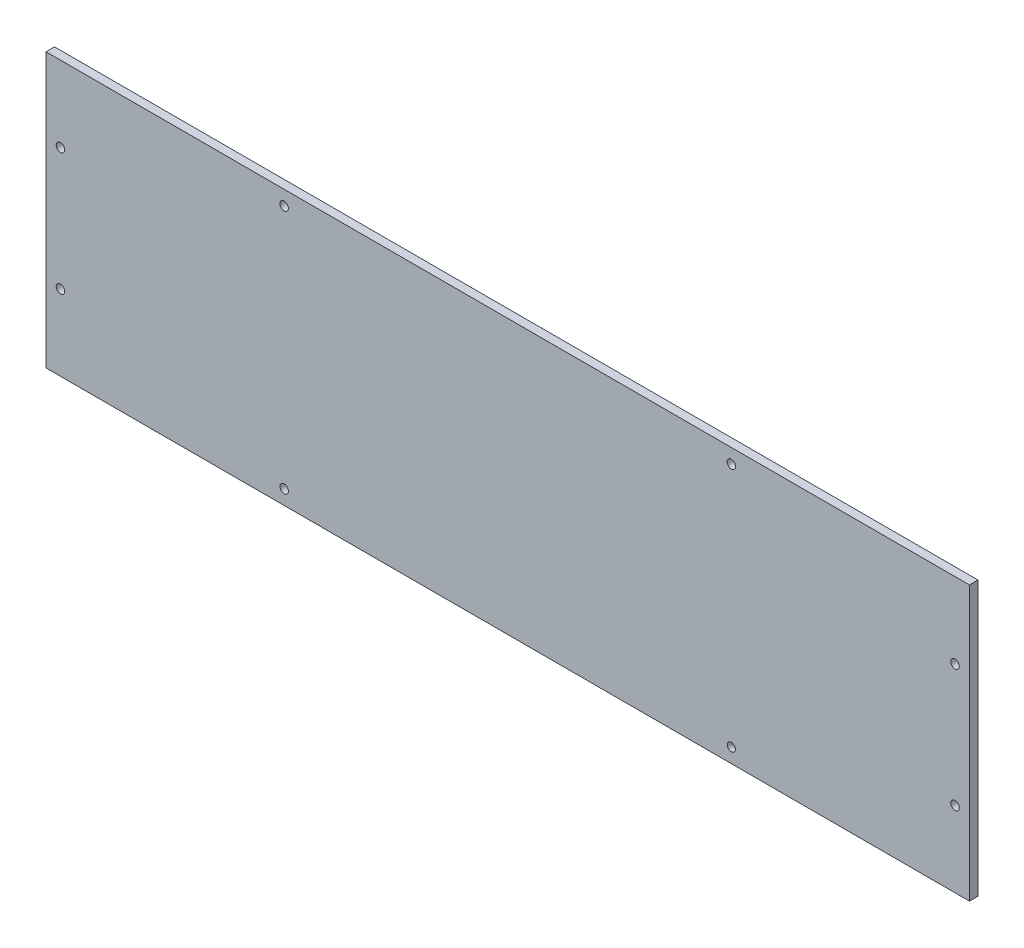
SolidWorks part; units mm, degrees
material "Acrylic (Medium-high impact)"
ref_plane "Front Plane" through (0, 0, 0) normal (0, 0, 1) x (1, 0, 0)
ref_plane "Top Plane" through (0, 0, 0) normal (0, 1, 0) x (1, 0, 0)
ref_plane "Right Plane" through (0, 0, 0) normal (1, 0, 0) x (0, 0, -1)
sketch "Model" plane through (0, 0, 0) normal (0, 0, 1) x (1, 0, 0)
  line L0 (0.0937, 96.2808) -> (324.895, 96.2808)
  line L1 (324.895, 96.2808) -> (324.895, 0.0799)
  line L2 (324.895, 0.0799) -> (0.0937, 0.0799)
  line L3 (0.0937, 0.0799) -> (0.0937, 96.2808)
  line L4 (129.892, 26.056) -> (133.194, 26.056)
  line L5 (133.194, 26.056) -> (133.194, 11.8553)
  line L6 (133.194, 11.8553) -> (129.892, 11.8553)
  line L7 (129.892, 11.8553) -> (129.892, 26.056)
  line L8 (153.694, 26.056) -> (156.994, 26.056)
  line L9 (156.994, 26.056) -> (156.994, 11.8553)
  line L10 (156.994, 11.8553) -> (153.694, 11.8553)
  line L11 (153.694, 11.8553) -> (153.694, 26.056)
  line L12 (167.992, 26.056) -> (171.294, 26.056)
  line L13 (171.294, 26.056) -> (171.294, 11.8553)
  line L14 (171.294, 11.8553) -> (167.992, 11.8553)
  line L15 (167.992, 11.8553) -> (167.992, 26.056)
  line L16 (191.794, 26.056) -> (195.094, 26.056)
  line L17 (195.094, 26.056) -> (195.094, 11.8553)
  line L18 (195.094, 11.8553) -> (191.794, 11.8553)
  line L19 (191.794, 11.8553) -> (191.794, 26.056)
  line L20 (12.6187, 26.6058) -> (26.6182, 26.6058)
  line L21 (26.6182, 26.6058) -> (26.6182, 12.6063)
  line L22 (26.6182, 12.6063) -> (12.6187, 12.6063)
  line L23 (12.6187, 12.6063) -> (12.6187, 26.6058)
  line L24 (31.6687, 26.6058) -> (45.6681, 26.6058)
  line L25 (45.6681, 26.6058) -> (45.6681, 12.6063)
  line L26 (45.6681, 12.6063) -> (31.6687, 12.6063)
  line L27 (31.6687, 12.6063) -> (31.6687, 26.6058)
  line L28 (50.7189, 26.6058) -> (64.7181, 26.6058)
  line L29 (64.7181, 26.6058) -> (64.7181, 12.6063)
  line L30 (64.7181, 12.6063) -> (50.7189, 12.6063)
  line L31 (50.7189, 12.6063) -> (50.7189, 26.6058)
  line L32 (69.7689, 26.6058) -> (83.7681, 26.6058)
  line L33 (83.7681, 26.6058) -> (83.7681, 12.6063)
  line L34 (83.7681, 12.6063) -> (69.7689, 12.6063)
  line L35 (69.7689, 12.6063) -> (69.7689, 26.6058)
  line L36 (136.444, 26.6058) -> (150.443, 26.6058)
  line L37 (150.443, 26.6058) -> (150.443, 12.6063)
  line L38 (150.443, 12.6063) -> (136.444, 12.6063)
  line L39 (136.444, 12.6063) -> (136.444, 26.6058)
  line L40 (174.544, 26.6058) -> (188.543, 26.6058)
  line L41 (188.543, 26.6058) -> (188.543, 12.6063)
  line L42 (188.543, 12.6063) -> (174.544, 12.6063)
  line L43 (174.544, 12.6063) -> (174.544, 26.6058)
  line L44 (241.219, 26.6058) -> (255.218, 26.6058)
  line L45 (255.218, 26.6058) -> (255.218, 12.6063)
  line L46 (255.218, 12.6063) -> (241.219, 12.6063)
  line L47 (241.219, 12.6063) -> (241.219, 26.6058)
  line L48 (260.269, 26.6058) -> (274.268, 26.6058)
  line L49 (274.268, 26.6058) -> (274.268, 12.6063)
  line L50 (274.268, 12.6063) -> (260.269, 12.6063)
  line L51 (260.269, 12.6063) -> (260.269, 26.6058)
  line L52 (279.319, 26.6058) -> (293.318, 26.6058)
  line L53 (293.318, 26.6058) -> (293.318, 12.6063)
  line L54 (293.318, 12.6063) -> (279.319, 12.6063)
  line L55 (279.319, 12.6063) -> (279.319, 26.6058)
  line L56 (298.369, 26.6058) -> (312.368, 26.6058)
  line L57 (312.368, 26.6058) -> (312.368, 12.6063)
  line L58 (312.368, 12.6063) -> (298.369, 12.6063)
  line L59 (298.369, 12.6063) -> (298.369, 26.6058)
  line L60 (15.5925, 45.1058) -> (18.8929, 45.1058)
  line L61 (18.8929, 45.1058) -> (18.8929, 30.9053)
  line L62 (18.8929, 30.9053) -> (15.5925, 30.9053)
  line L63 (15.5925, 30.9053) -> (15.5925, 45.1058)
  line L64 (39.394, 45.1058) -> (42.6932, 45.1058)
  line L65 (42.6932, 45.1058) -> (42.6932, 30.9053)
  line L66 (42.6932, 30.9053) -> (39.394, 30.9053)
  line L67 (39.394, 30.9053) -> (39.394, 45.1058)
  line L68 (282.294, 45.1058) -> (285.594, 45.1058)
  line L69 (285.594, 45.1058) -> (285.594, 30.9053)
  line L70 (285.594, 30.9053) -> (282.294, 30.9053)
  line L71 (282.294, 30.9053) -> (282.294, 45.1058)
  line L72 (306.094, 45.1058) -> (309.394, 45.1058)
  line L73 (309.394, 45.1058) -> (309.394, 30.9053)
  line L74 (309.394, 30.9053) -> (306.094, 30.9053)
  line L75 (306.094, 30.9053) -> (306.094, 45.1058)
  line L76 (22.1423, 45.6558) -> (36.1431, 45.6558)
  line L77 (36.1431, 45.6558) -> (36.1431, 31.6563)
  line L78 (36.1431, 31.6563) -> (22.1423, 31.6563)
  line L79 (22.1423, 31.6563) -> (22.1423, 45.6558)
  line L80 (50.7189, 45.6558) -> (64.7181, 45.6558)
  line L81 (64.7181, 45.6558) -> (64.7181, 31.6563)
  line L82 (64.7181, 31.6563) -> (50.7189, 31.6563)
  line L83 (50.7189, 31.6563) -> (50.7189, 45.6558)
  line L84 (69.7689, 45.6558) -> (83.7681, 45.6558)
  line L85 (83.7681, 45.6558) -> (83.7681, 31.6563)
  line L86 (83.7681, 31.6563) -> (69.7689, 31.6563)
  line L87 (69.7689, 31.6563) -> (69.7689, 45.6558)
  line L88 (88.8189, 45.6558) -> (102.818, 45.6558)
  line L89 (102.818, 45.6558) -> (102.818, 31.6563)
  line L90 (102.818, 31.6563) -> (88.8189, 31.6563)
  line L91 (88.8189, 31.6563) -> (88.8189, 45.6558)
  line L92 (107.867, 45.6558) -> (121.868, 45.6558)
  line L93 (121.868, 45.6558) -> (121.868, 31.6563)
  line L94 (121.868, 31.6563) -> (107.867, 31.6563)
  line L95 (107.867, 31.6563) -> (107.867, 45.6558)
  line L96 (126.919, 45.6558) -> (140.918, 45.6558)
  line L97 (140.918, 45.6558) -> (140.918, 31.6563)
  line L98 (140.918, 31.6563) -> (126.919, 31.6563)
  line L99 (126.919, 31.6563) -> (126.919, 45.6558)
  line L100 (145.969, 45.6558) -> (159.968, 45.6558)
  line L101 (159.968, 45.6558) -> (159.968, 31.6563)
  line L102 (159.968, 31.6563) -> (145.969, 31.6563)
  line L103 (145.969, 31.6563) -> (145.969, 45.6558)
  line L104 (165.019, 45.6558) -> (179.018, 45.6558)
  line L105 (179.018, 45.6558) -> (179.018, 31.6563)
  line L106 (179.018, 31.6563) -> (165.019, 31.6563)
  line L107 (165.019, 31.6563) -> (165.019, 45.6558)
  line L108 (184.069, 45.6558) -> (198.068, 45.6558)
  line L109 (198.068, 45.6558) -> (198.068, 31.6563)
  line L110 (198.068, 31.6563) -> (184.069, 31.6563)
  line L111 (184.069, 31.6563) -> (184.069, 45.6558)
  line L112 (203.119, 45.6558) -> (217.118, 45.6558)
  line L113 (217.118, 45.6558) -> (217.118, 31.6563)
  line L114 (217.118, 31.6563) -> (203.119, 31.6563)
  line L115 (203.119, 31.6563) -> (203.119, 45.6558)
  line L116 (222.169, 45.6558) -> (236.168, 45.6558)
  line L117 (236.168, 45.6558) -> (236.168, 31.6563)
  line L118 (236.168, 31.6563) -> (222.169, 31.6563)
  line L119 (222.169, 31.6563) -> (222.169, 45.6558)
  line L120 (241.219, 45.6558) -> (255.218, 45.6558)
  line L121 (255.218, 45.6558) -> (255.218, 31.6563)
  line L122 (255.218, 31.6563) -> (241.219, 31.6563)
  line L123 (241.219, 31.6563) -> (241.219, 45.6558)
  line L124 (260.269, 45.6558) -> (274.268, 45.6558)
  line L125 (274.268, 45.6558) -> (274.268, 31.6563)
  line L126 (274.268, 31.6563) -> (260.269, 31.6563)
  line L127 (260.269, 31.6563) -> (260.269, 45.6558)
  line L128 (288.844, 45.6558) -> (302.843, 45.6558)
  line L129 (302.843, 45.6558) -> (302.843, 31.6563)
  line L130 (302.843, 31.6563) -> (288.844, 31.6563)
  line L131 (288.844, 31.6563) -> (288.844, 45.6558)
  line L132 (12.6187, 64.7058) -> (26.6182, 64.7058)
  line L133 (26.6182, 64.7058) -> (26.6182, 50.7062)
  line L134 (26.6182, 50.7062) -> (12.6187, 50.7062)
  line L135 (12.6187, 50.7062) -> (12.6187, 64.7058)
  line L136 (31.6687, 64.7058) -> (45.6681, 64.7058)
  line L137 (45.6681, 64.7058) -> (45.6681, 50.7062)
  line L138 (45.6681, 50.7062) -> (31.6687, 50.7062)
  line L139 (31.6687, 50.7062) -> (31.6687, 64.7058)
  line L140 (50.7189, 64.7058) -> (64.7181, 64.7058)
  line L141 (64.7181, 64.7058) -> (64.7181, 50.7062)
  line L142 (64.7181, 50.7062) -> (50.7189, 50.7062)
  line L143 (50.7189, 50.7062) -> (50.7189, 64.7058)
  line L144 (69.7689, 64.7058) -> (83.7681, 64.7058)
  line L145 (83.7681, 64.7058) -> (83.7681, 50.7062)
  line L146 (83.7681, 50.7062) -> (69.7689, 50.7062)
  line L147 (69.7689, 50.7062) -> (69.7689, 64.7058)
  line L148 (88.8189, 64.7058) -> (102.818, 64.7058)
  line L149 (102.818, 64.7058) -> (102.818, 50.7062)
  line L150 (102.818, 50.7062) -> (88.8189, 50.7062)
  line L151 (88.8189, 50.7062) -> (88.8189, 64.7058)
  line L152 (107.867, 64.7058) -> (121.868, 64.7058)
  line L153 (121.868, 64.7058) -> (121.868, 50.7062)
  line L154 (121.868, 50.7062) -> (107.867, 50.7062)
  line L155 (107.867, 50.7062) -> (107.867, 64.7058)
  line L156 (126.919, 64.7058) -> (140.918, 64.7058)
  line L157 (140.918, 64.7058) -> (140.918, 50.7062)
  line L158 (140.918, 50.7062) -> (126.919, 50.7062)
  line L159 (126.919, 50.7062) -> (126.919, 64.7058)
  line L160 (145.969, 64.7058) -> (159.968, 64.7058)
  line L161 (159.968, 64.7058) -> (159.968, 50.7062)
  line L162 (159.968, 50.7062) -> (145.969, 50.7062)
  line L163 (145.969, 50.7062) -> (145.969, 64.7058)
  line L164 (165.019, 64.7058) -> (179.018, 64.7058)
  line L165 (179.018, 64.7058) -> (179.018, 50.7062)
  line L166 (179.018, 50.7062) -> (165.019, 50.7062)
  line L167 (165.019, 50.7062) -> (165.019, 64.7058)
  line L168 (184.069, 64.7058) -> (198.068, 64.7058)
  line L169 (198.068, 64.7058) -> (198.068, 50.7062)
  line L170 (198.068, 50.7062) -> (184.069, 50.7062)
  line L171 (184.069, 50.7062) -> (184.069, 64.7058)
  line L172 (203.119, 64.7058) -> (217.118, 64.7058)
  line L173 (217.118, 64.7058) -> (217.118, 50.7062)
  line L174 (217.118, 50.7062) -> (203.119, 50.7062)
  line L175 (203.119, 50.7062) -> (203.119, 64.7058)
  line L176 (222.169, 64.7058) -> (236.168, 64.7058)
  line L177 (236.168, 64.7058) -> (236.168, 50.7062)
  line L178 (236.168, 50.7062) -> (222.169, 50.7062)
  line L179 (222.169, 50.7062) -> (222.169, 64.7058)
  line L180 (241.219, 64.7058) -> (255.218, 64.7058)
  line L181 (255.218, 64.7058) -> (255.218, 50.7062)
  line L182 (255.218, 50.7062) -> (241.219, 50.7062)
  line L183 (241.219, 50.7062) -> (241.219, 64.7058)
  line L184 (260.269, 64.7058) -> (274.268, 64.7058)
  line L185 (274.268, 64.7058) -> (274.268, 50.7062)
  line L186 (274.268, 50.7062) -> (260.269, 50.7062)
  line L187 (260.269, 50.7062) -> (260.269, 64.7058)
  line L188 (279.319, 64.7058) -> (293.318, 64.7058)
  line L189 (293.318, 64.7058) -> (293.318, 50.7062)
  line L190 (293.318, 50.7062) -> (279.319, 50.7062)
  line L191 (279.319, 50.7062) -> (279.319, 64.7058)
  line L192 (298.369, 64.7058) -> (312.368, 64.7058)
  line L193 (312.368, 64.7058) -> (312.368, 50.7062)
  line L194 (312.368, 50.7062) -> (298.369, 50.7062)
  line L195 (298.369, 50.7062) -> (298.369, 64.7058)
  line L196 (15.5925, 83.2058) -> (18.8929, 83.2058)
  line L197 (18.8929, 83.2058) -> (18.8929, 69.0051)
  line L198 (18.8929, 69.0051) -> (15.5925, 69.0051)
  line L199 (15.5925, 69.0051) -> (15.5925, 83.2058)
  line L200 (39.394, 83.2058) -> (42.6932, 83.2058)
  line L201 (42.6932, 83.2058) -> (42.6932, 69.0051)
  line L202 (42.6932, 69.0051) -> (39.394, 69.0051)
  line L203 (39.394, 69.0051) -> (39.394, 83.2058)
  line L204 (282.294, 83.2058) -> (285.594, 83.2058)
  line L205 (285.594, 83.2058) -> (285.594, 69.0051)
  line L206 (285.594, 69.0051) -> (282.294, 69.0051)
  line L207 (282.294, 69.0051) -> (282.294, 83.2058)
  line L208 (306.094, 83.2058) -> (309.394, 83.2058)
  line L209 (309.394, 83.2058) -> (309.394, 69.0051)
  line L210 (309.394, 69.0051) -> (306.094, 69.0051)
  line L211 (306.094, 69.0051) -> (306.094, 83.2058)
  line L212 (22.1423, 83.7558) -> (36.1431, 83.7558)
  line L213 (36.1431, 83.7558) -> (36.1431, 69.7562)
  line L214 (36.1431, 69.7562) -> (22.1423, 69.7562)
  line L215 (22.1423, 69.7562) -> (22.1423, 83.7558)
  line L216 (50.7189, 83.7558) -> (64.7181, 83.7558)
  line L217 (64.7181, 83.7558) -> (64.7181, 69.7562)
  line L218 (64.7181, 69.7562) -> (50.7189, 69.7562)
  line L219 (50.7189, 69.7562) -> (50.7189, 83.7558)
  line L220 (69.7689, 83.7558) -> (83.7681, 83.7558)
  line L221 (83.7681, 83.7558) -> (83.7681, 69.7562)
  line L222 (83.7681, 69.7562) -> (69.7689, 69.7562)
  line L223 (69.7689, 69.7562) -> (69.7689, 83.7558)
  line L224 (88.8189, 83.7558) -> (102.818, 83.7558)
  line L225 (102.818, 83.7558) -> (102.818, 69.7562)
  line L226 (102.818, 69.7562) -> (88.8189, 69.7562)
  line L227 (88.8189, 69.7562) -> (88.8189, 83.7558)
  line L228 (107.867, 83.7558) -> (121.868, 83.7558)
  line L229 (121.868, 83.7558) -> (121.868, 69.7562)
  line L230 (121.868, 69.7562) -> (107.867, 69.7562)
  line L231 (107.867, 69.7562) -> (107.867, 83.7558)
  line L232 (126.919, 83.7558) -> (140.918, 83.7558)
  line L233 (140.918, 83.7558) -> (140.918, 69.7562)
  line L234 (140.918, 69.7562) -> (126.919, 69.7562)
  line L235 (126.919, 69.7562) -> (126.919, 83.7558)
  line L236 (145.969, 83.7558) -> (159.968, 83.7558)
  line L237 (159.968, 83.7558) -> (159.968, 69.7562)
  line L238 (159.968, 69.7562) -> (145.969, 69.7562)
  line L239 (145.969, 69.7562) -> (145.969, 83.7558)
  line L240 (165.019, 83.7558) -> (179.018, 83.7558)
  line L241 (179.018, 83.7558) -> (179.018, 69.7562)
  line L242 (179.018, 69.7562) -> (165.019, 69.7562)
  line L243 (165.019, 69.7562) -> (165.019, 83.7558)
  line L244 (184.069, 83.7558) -> (198.068, 83.7558)
  line L245 (198.068, 83.7558) -> (198.068, 69.7562)
  line L246 (198.068, 69.7562) -> (184.069, 69.7562)
  line L247 (184.069, 69.7562) -> (184.069, 83.7558)
  line L248 (203.119, 83.7558) -> (217.118, 83.7558)
  line L249 (217.118, 83.7558) -> (217.118, 69.7562)
  line L250 (217.118, 69.7562) -> (203.119, 69.7562)
  line L251 (203.119, 69.7562) -> (203.119, 83.7558)
  line L252 (222.169, 83.7558) -> (236.168, 83.7558)
  line L253 (236.168, 83.7558) -> (236.168, 69.7562)
  line L254 (236.168, 69.7562) -> (222.169, 69.7562)
  line L255 (222.169, 69.7562) -> (222.169, 83.7558)
  line L256 (241.219, 83.7558) -> (255.218, 83.7558)
  line L257 (255.218, 83.7558) -> (255.218, 69.7562)
  line L258 (255.218, 69.7562) -> (241.219, 69.7562)
  line L259 (241.219, 69.7562) -> (241.219, 83.7558)
  line L260 (260.269, 83.7558) -> (274.268, 83.7558)
  line L261 (274.268, 83.7558) -> (274.268, 69.7562)
  line L262 (274.268, 69.7562) -> (260.269, 69.7562)
  line L263 (260.269, 69.7562) -> (260.269, 83.7558)
  line L264 (288.844, 83.7558) -> (302.843, 83.7558)
  line L265 (302.843, 83.7558) -> (302.843, 69.7562)
  line L266 (302.843, 69.7562) -> (288.844, 69.7562)
  line L267 (288.844, 69.7562) -> (288.844, 83.7558)
  line L272 (10.0937, 86.2808) -> (10.0937, 10.0799)
  line L273 (10.0937, 10.0799) -> (314.895, 10.0799)
  line L274 (314.895, 10.0799) -> (314.895, 86.2808)
  line L275 (314.895, 86.2808) -> (10.0937, 86.2808)
  point P273 (83.794, 5.0799)
  point P274 (241.1947, 91.2808)
  point P276 (10.0937, 86.2808)
  point P277 (10.0937, 10.0799)
  point P278 (314.895, 10.0799)
  point P279 (314.895, 86.2808)
  point P292 (5.0937, 58.9555)
  point P293 (319.895, 15.855)
  point P305 (5.0937, 26.6301)
  point P306 (83.794, 91.2808)
  point P307 (241.1947, 5.0799)
  point P308 (319.895, 69.7306)
extrude "Boss-Extrude2" add sketch "Model" along normal blind 1.5 contours L274 L275 L272 L273 L266 L267 L264 L265 L262 L263 L260 L261 L258 L259 L256 L257 L254 L255 L252 L253 L250 L251 L248 L249 L246 L247 L244 L245 L242 L243 L240 L241 L238 L239 L236 L237 L234 L235 L232 L233 L230 region at (162.4966, 46.1945, 0)
sketch "Sketch1" plane through (0, 0, 1.5) normal (0, 0, 1) x (1, 0, 0)
  point P0 (29.1427, 76.756)
  point P1 (143.4435, 19.606)
  point P3 (29.1427, 38.6561)
  point P4 (181.5435, 19.606)
  point P8 (229.1685, 38.6561)
  point P9 (229.1685, 57.706)
  point P10 (229.1685, 76.756)
  point P11 (210.1185, 76.756)
  point P12 (295.8435, 38.6561)
  point P13 (286.3185, 19.606)
  point P14 (286.3185, 57.706)
  point P15 (305.3685, 19.606)
  point P16 (305.3685, 57.706)
  point P17 (210.1185, 57.706)
  point P19 (210.1185, 38.6561)
  point P20 (191.0685, 38.6561)
  point P24 (191.0685, 57.706)
  point P29 (191.0685, 76.756)
  point P30 (172.0185, 76.756)
  point P36 (172.0185, 57.706)
  point P39 (172.0185, 38.6561)
  point P40 (152.9685, 38.6561)
  point P41 (152.9685, 57.706)
  point P42 (152.9685, 76.756)
  point P45 (133.9185, 76.756)
  point P46 (133.9185, 57.706)
  point P49 (133.9185, 38.6561)
  point P50 (114.8675, 38.6561)
  point P53 (114.8675, 57.706)
  point P54 (114.8675, 76.756)
  point P57 (95.8184, 76.756)
  point P61 (95.8185, 57.706)
  point P62 (95.8184, 38.6561)
  point P65 (76.7685, 38.6561)
  point P67 (76.7685, 57.706)
  point P69 (76.7685, 76.756)
  point P70 (57.7185, 76.756)
  point P73 (57.7185, 57.706)
  point P75 (57.7185, 38.6561)
  point P77 (57.7185, 19.606)
  point P80 (19.6185, 19.606)
  point P81 (38.6684, 19.606)
  point P86 (76.7685, 19.606)
  point P89 (38.6684, 57.706)
  point P90 (19.6185, 57.706)
  point P223 (295.8435, 76.756)
  point P224 (267.2685, 19.606)
  point P225 (267.2685, 38.6561)
  point P226 (267.2685, 57.706)
  point P227 (267.2685, 76.756)
  point P228 (248.2185, 76.756)
  point P229 (248.2185, 57.706)
  point P230 (248.2185, 38.6561)
  point P231 (248.2185, 19.606)
sketch "Sketch2" plane through (0, 0, 0) normal (0, 0, 1) x (1, 0, 0)
  point P0 (29.1427, 76.756)
  point P1 (143.4435, 19.606)
  point P3 (29.1427, 38.6561)
  point P4 (181.5435, 19.606)
  point P8 (229.1685, 38.6561)
  point P9 (229.1685, 57.706)
  point P10 (229.1685, 76.756)
  point P11 (210.1185, 76.756)
  point P12 (295.8435, 38.6561)
  point P13 (286.3185, 19.606)
  point P14 (286.3185, 57.706)
  point P15 (305.3685, 19.606)
  point P16 (305.3685, 57.706)
  point P17 (210.1185, 57.706)
  point P19 (210.1185, 38.6561)
  point P20 (191.0685, 38.6561)
  point P24 (191.0685, 57.706)
  point P29 (191.0685, 76.756)
  point P30 (172.0185, 76.756)
  point P36 (172.0185, 57.706)
  point P39 (172.0185, 38.6561)
  point P40 (152.9685, 38.6561)
  point P41 (152.9685, 57.706)
  point P42 (152.9685, 76.756)
  point P45 (133.9185, 76.756)
  point P46 (133.9185, 57.706)
  point P49 (133.9185, 38.6561)
  point P50 (114.8675, 38.6561)
  point P53 (114.8675, 57.706)
  point P54 (114.8675, 76.756)
  point P57 (95.8184, 76.756)
  point P61 (95.8185, 57.706)
  point P62 (95.8184, 38.6561)
  point P65 (76.7685, 38.6561)
  point P67 (76.7685, 57.706)
  point P69 (76.7685, 76.756)
  point P70 (57.7185, 76.756)
  point P73 (57.7185, 57.706)
  point P75 (57.7185, 38.6561)
  point P77 (57.7185, 19.606)
  point P80 (19.6185, 19.606)
  point P81 (38.6684, 19.606)
  point P86 (76.7685, 19.606)
  point P89 (38.6684, 57.706)
  point P90 (19.6185, 57.706)
  point P223 (295.8435, 76.756)
  point P224 (267.2685, 19.606)
  point P225 (267.2685, 38.6561)
  point P226 (267.2685, 57.706)
  point P227 (267.2685, 76.756)
  point P228 (248.2185, 76.756)
  point P229 (248.2185, 57.706)
  point P230 (248.2185, 38.6561)
  point P231 (248.2185, 19.606)
ref_axis "Axis2" through (305.3685, 19.606, 0) along (0, 0, 1)
ref_axis "Axis3" through (286.3185, 19.606, 0) along (0, 0, 1)
ref_axis "Axis4" through (295.8435, 38.6561, 0) along (0, 0, 1)
ref_axis "Axis5" through (267.2685, 38.6561, 0) along (0, 0, 1)
ref_axis "Axis6" through (286.3185, 57.706, 0) along (0, 0, 1)
ref_axis "Axis7" through (305.3685, 57.706, 0) along (0, 0, 1)
ref_axis "Axis8" through (295.8435, 76.756, 0) along (0, 0, 1)
ref_axis "Axis9" through (267.2685, 76.756, 0) along (0, 0, 1)
ref_axis "Axis10" through (248.2185, 76.756, 0) along (0, 0, 1)
ref_axis "Axis11" through (229.1685, 76.756, 0) along (0, 0, 1)
ref_axis "Axis12" through (210.1185, 76.756, 0) along (0, 0, 1)
ref_axis "Axis13" through (267.2685, 57.706, 0) along (0, 0, 1)
ref_axis "Axis14" through (248.2185, 57.706, 0) along (0, 0, 1)
ref_axis "Axis15" through (229.1685, 57.706, 0) along (0, 0, 1)
ref_axis "Axis16" through (191.0685, 76.756, 0) along (0, 0, 1)
ref_axis "Axis17" through (172.0185, 76.756, 0) along (0, 0, 1)
ref_axis "Axis18" through (152.9685, 76.756, 0) along (0, 0, 1)
ref_axis "Axis19" through (133.9185, 76.756, 0) along (0, 0, 1)
ref_axis "Axis20" through (114.8675, 76.756, 0) along (0, 0, 1)
ref_axis "Axis21" through (95.8184, 76.756, 0) along (0, 0, 1)
ref_axis "Axis22" through (76.7685, 76.756, 0) along (0, 0, 1)
ref_axis "Axis23" through (57.7185, 76.756, 0) along (0, 0, 1)
ref_axis "Axis24" through (29.1427, 76.756, 0) along (0, 0, 1)
ref_axis "Axis25" through (19.6185, 57.706, 0) along (0, 0, 1)
ref_axis "Axis26" through (38.6684, 57.706, 0) along (0, 0, 1)
ref_axis "Axis27" through (57.7185, 57.706, 0) along (0, 0, 1)
ref_axis "Axis28" through (76.7685, 57.706, 0) along (0, 0, 1)
ref_axis "Axis29" through (95.8185, 57.706, 0) along (0, 0, 1)
ref_axis "Axis30" through (114.8675, 57.706, 0) along (0, 0, 1)
ref_axis "Axis31" through (133.9185, 57.706, 0) along (0, 0, 1)
ref_axis "Axis32" through (172.0185, 57.706, 0) along (0, 0, 1)
ref_axis "Axis33" through (152.9685, 57.706, 0) along (0, 0, 1)
ref_axis "Axis34" through (191.0685, 57.706, 0) along (0, 0, 1)
ref_axis "Axis35" through (210.1185, 57.706, 0) along (0, 0, 1)
ref_axis "Axis38" through (248.2185, 38.6561, 0) along (0, 0, 1)
ref_axis "Axis39" through (229.1685, 38.6561, 0) along (0, 0, 1)
ref_axis "Axis40" through (210.1185, 38.6561, 0) along (0, 0, 1)
ref_axis "Axis41" through (191.0685, 38.6561, 0) along (0, 0, 1)
ref_axis "Axis42" through (172.0185, 38.6561, 0) along (0, 0, 1)
ref_axis "Axis43" through (152.9685, 38.6561, 0) along (0, 0, 1)
ref_axis "Axis44" through (267.2685, 19.606, 0) along (0, 0, 1)
ref_axis "Axis45" through (248.2185, 19.606, 0) along (0, 0, 1)
ref_axis "Axis46" through (181.5435, 19.606, 0) along (0, 0, 1)
ref_axis "Axis47" through (133.9185, 38.6561, 0) along (0, 0, 1)
ref_axis "Axis48" through (143.4435, 19.606, 0) along (0, 0, 1)
ref_axis "Axis49" through (114.8675, 38.6561, 0) along (0, 0, 1)
ref_axis "Axis50" through (95.8184, 38.6561, 0) along (0, 0, 1)
ref_axis "Axis51" through (76.7685, 38.6561, 0) along (0, 0, 1)
ref_axis "Axis52" through (57.7185, 38.6561, 0) along (0, 0, 1)
ref_axis "Axis53" through (29.1427, 38.6561, 0) along (0, 0, 1)
ref_axis "Axis54" through (19.6185, 19.606, 0) along (0, 0, 1)
ref_axis "Axis55" through (38.6684, 19.606, 0) along (0, 0, 1)
ref_axis "Axis56" through (57.7185, 19.606, 1.5) along (0, 0, -1)
ref_axis "Axis57" through (76.7685, 19.606, 1.5) along (0, 0, -1)
sketch "Sketch3" plane through (0, 0, 1.5) normal (0, 0, 1) x (1, 0, 0)
  line L1 (0, 0) -> (324.9887, 0)
  line L2 (0, 0) -> (0, 96.3745)
  line L3 (10.0937, 86.2808) -> (314.895, 86.2808)
  line L4 (10.0937, 86.2808) -> (10.0937, 10.0799)
  line L5 (0, 96.3745) -> (324.9887, 96.3745)
  line L6 (324.9887, 0) -> (324.9887, 96.3745)
  line L7 (10.0937, 10.0799) -> (314.895, 10.0799)
  line L8 (314.895, 86.2808) -> (314.895, 10.0799)
  point P21 (324.9887, 0)
  point P22 (324.9887, 96.3745)
  point P23 (0, 96.3745)
  point P24 (0, 0)
extrude "Boss-Extrude4" add sketch "Sketch3" against normal blind 1.5
sketch "Sketch4" plane through (0, 0, 0) normal (0, 0, 1) x (1, 0, 0)
  circle A0 centre (5.0937, 69.7306) radius 1.5
  circle A1 centre (5.0937, 26.6301) radius 1.5
  circle A2 centre (83.794, 5.0799) radius 1.5
  circle A3 centre (241.1947, 5.0799) radius 1.5
  circle A4 centre (319.895, 26.6301) radius 1.5
  circle A5 centre (319.895, 69.7306) radius 1.5
  circle A6 centre (241.1947, 91.2808) radius 1.5
  circle A7 centre (83.794, 91.2808) radius 1.5
  point P6 (5.0937, 69.7306)
  point P7 (319.895, 26.6301)
  point P273 (83.794, 5.0799)
  point P274 (241.1947, 91.2808)
  point P305 (5.0937, 26.6301)
  point P306 (83.794, 91.2808)
  point P307 (241.1947, 5.0799)
  point P308 (319.895, 69.7306)
extrude "Cut-Extrude2" cut sketch "Sketch4" along normal blind 2.54
sketch "Sketch5" plane through (0, 0, 1.5) normal (0, 0, 1) x (1, 0, 0)
  line L0 (114.2228, 12.6063) -> (12.6187, 12.6063)
  line L2 (312.368, 64.7058) -> (312.368, 12.6063)
  line L3 (312.368, 12.6063) -> (207.0166, 12.6063)
  line L4 (12.6187, 64.7058) -> (12.6187, 12.6063)
  line L6 (12.6187, 64.7058) -> (12.6187, 85.3282)
  line L7 (12.6187, 85.3282) -> (312.368, 85.3282)
  line L8 (312.368, 64.7058) -> (312.368, 85.3282)
  line L10 (114.2228, 12.6063) -> (114.2228, 7.2971)
  line L11 (114.2228, 7.2971) -> (207.0166, 7.2971)
  line L12 (207.0166, 12.6063) -> (207.0166, 7.2971)
extrude "Boss-Extrude5" add sketch "Sketch5" against normal blind 1.5
sketch "Sketch6" plane through (0, 0, 1.5) normal (0, 0, 1) x (1, 0, 0)
  line L1 (0, 96.3745) -> (324.9887, 96.3745)
  line L2 (0, 96.3745) -> (0, 0)
  line L3 (0, 0) -> (324.9887, 0)
  line L4 (324.9887, 96.3745) -> (324.9887, 0)
  circle A0 centre (319.895, 69.7306) radius 1.5
  circle A1 centre (319.895, 26.6301) radius 1.5
  circle A2 centre (241.1947, 5.0799) radius 1.438
  circle A3 centre (241.1947, 91.2808) radius 1.5
  circle A4 centre (5.0937, 26.6301) radius 1.5
  circle A5 centre (83.794, 5.0799) radius 1.5
  circle A6 centre (83.794, 91.2808) radius 1.5
  circle A7 centre (5.0937, 69.7306) radius 1.5
extrude "Boss-Extrude6" add sketch "Sketch6" along normal blind 1.5
